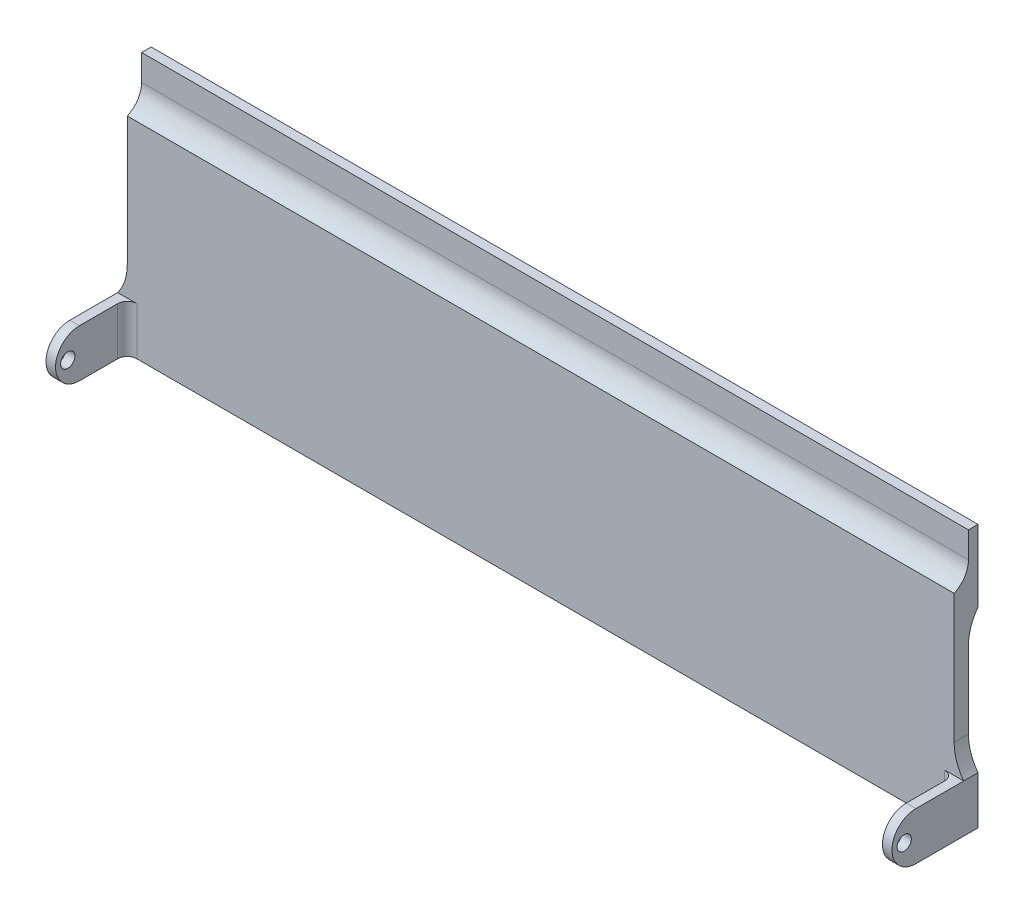
SolidWorks part; units mm, degrees
ref_plane "Front Plane" through (0, 0, 0) normal (0, 0, 1) x (1, 0, 0)
ref_plane "Top Plane" through (0, 0, 0) normal (0, 1, 0) x (1, 0, 0)
ref_plane "Right Plane" through (0, 0, 0) normal (1, 0, 0) x (0, 0, -1)
sketch "Sketch1" plane through (0, 0, 0) normal (0, 0, 1) x (1, 0, 0)
  line L1 (-86.5, -21.5) -> (86.5, -21.5)
  line L2 (-86.5, -21.5) -> (-86.5, 21.5)
  line L3 (-86.5, 21.5) -> (86.5, 21.5)
  line L4 (86.5, -21.5) -> (86.5, 21.5)
  line L5 (-86.5, -21.5) -> (86.5, 21.5) construction
  line L6 (-86.5, 21.5) -> (86.5, -21.5) construction
  point P0 (0, 0)
  dimension "D1" = 173
  dimension "D2" = 43
extrude "Boss-Extrude1" add sketch "Sketch1" along normal blind 3
sketch "Sketch2" plane through (-86.5, 0, 0) normal (-1, 0, 0) x (0, 0, 1)
  line L0 (3, 21.5) -> (3, -21.5) construction
  line L1 (0, -21.5) -> (13, -21.5)
  line L2 (0, -21.5) -> (0, -11.5)
  line L3 (0, -11.5) -> (13, -11.5)
  line L4 (13, -21.5) -> (13, -11.5)
  circle A0 centre (13, -16.5) radius 5
  dimension "D1" = 10
  dimension "D2" = 10
extrude "Boss-Extrude2" add sketch "Sketch2" along normal blind 2 contours L2 L1 L4 L3 | A0
sketch "Sketch3" plane through (86.5, 0, 0) normal (1, 0, 0) x (0, 0, -1)
  line L1 (0, -21.5) -> (-13, -21.5)
  line L2 (0, -21.5) -> (0, -11.5)
  line L3 (0, -11.5) -> (-13, -11.5)
  line L4 (-13, -21.5) -> (-13, -11.5)
  circle A0 centre (-13, -16.5) radius 5
extrude "Boss-Extrude3" add sketch "Sketch3" along normal blind 2 contours L2 L1 L4 L3 | A0
sketch "Sketch4" plane through (88.5, 0, 0) normal (1, 0, 0) x (0, 0, -1)
  circle A0 centre (-15.4465, -16.5) radius 1.5
  dimension "D1" = 3
extrude "Cut-Extrude1" cut sketch "Sketch4" against normal blind 200
sketch "Sketch5" plane through (0, 0, 0) normal (0, 0, -1) x (-1, 0, 0)
  line L0 (-86.5, -11.5) -> (-86.5, 21.5) construction
  line L1 (-86.5, 16.5) -> (86.5, 16.5)
  line L2 (-86.5, 16.5) -> (-86.5, 31.5)
  line L3 (-86.5, 31.5) -> (86.5, 31.5)
  line L4 (86.5, 16.5) -> (86.5, 31.5)
  line L5 (-86.5, 21.5) -> (86.5, 21.5) construction
  dimension "D1" = 173
  dimension "D2" = 10
  dimension "D3" = 5
extrude "Boss-Extrude4" add sketch "Sketch5" along normal blind 2
fillet "Fillet1" radius 10 1 edges at (0, 16.5, 0)
fillet "Fillet2" radius 10 2 edges at (-86.5, -11.5, 1.5) (86.5, -11.5, 1.5)
fillet "Fillet3" radius 5 1 edges at (0, 21.5, 0)
fillet "Fillet4" radius 2 2 edges at (-86.5, -16.5, 3) (86.5, -16.5, 3)
